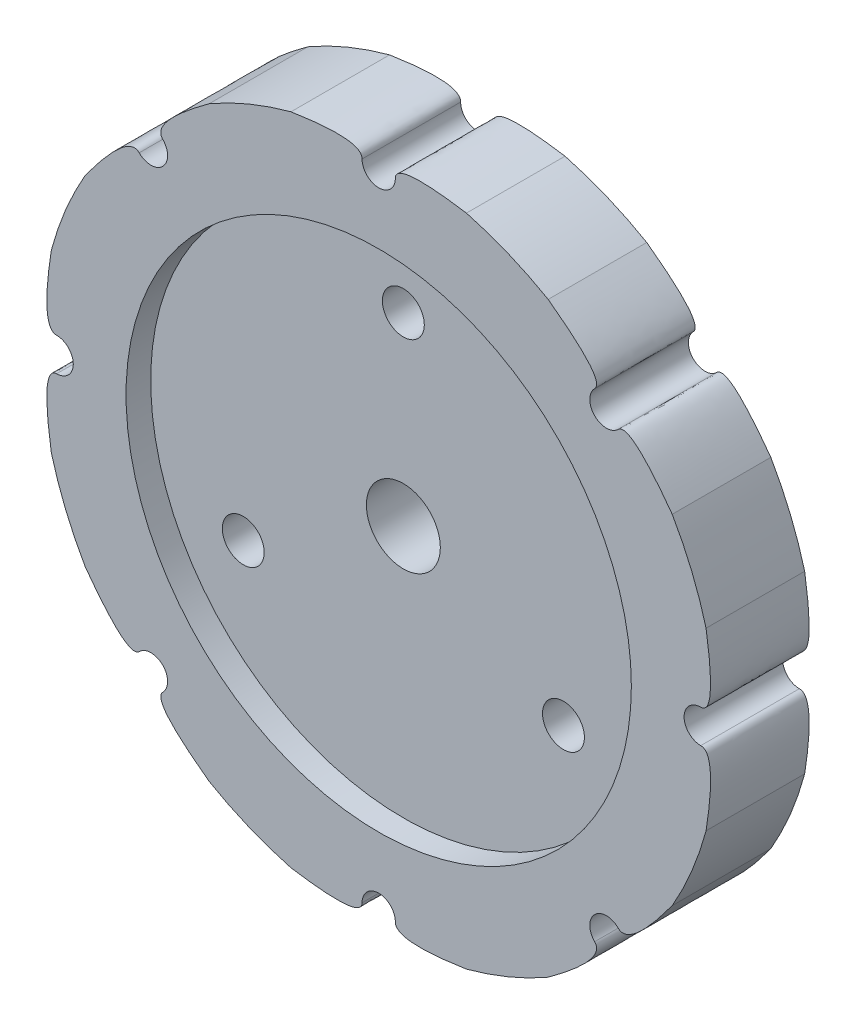
SolidWorks part; units mm, degrees
ref_plane "Plan de face" through (0, 0, 0) normal (0, 0, 1) x (1, 0, 0)
ref_plane "Plan de dessus" through (0, 0, 0) normal (0, 1, 0) x (1, 0, 0)
ref_plane "Plan de droite" through (0, 0, 0) normal (1, 0, 0) x (0, 0, -1)
sketch "Esquisse1" plane through (0, 0, 0) normal (0, 0, 1) x (1, 0, 0)
  circle A0 centre (0, 0) radius 27.5
  dimension "D1" = 55
extrude "Boss.-Extru.1" add sketch "Esquisse1" along normal mid plane 8
ref_axis "Axe1" through (0, 0, 4) along (0, 0, -1)
sketch "Esquisse2" plane through (0, 0, 0) normal (0, 0, 1) x (1, 0, 0)
  line L0 (0, 0) -> (0, 42.1559) construction
  line L1 (1.35, 26.1313) -> (1.35, 27.4668) construction
  line L2 (1.35, 27.4668) -> (7.1175, 26.563) construction
  line L3 (0, 0) -> (-7.1175, 26.563) construction
  line L4 (-1.35, 26.1313) -> (-1.35, 27.4668) construction
  line L5 (-1.35, 27.4668) -> (-7.1175, 26.563) construction
  line L6 (0, 0) -> (7.1175, 26.563) construction
  line L7 (0, 26.1313) -> (-18.4776, 18.4776) construction
  line L8 (-18.4776, 18.4776) -> (-26.1313, 0) construction
  line L9 (-26.1313, 0) -> (-18.4776, -18.4776) construction
  line L10 (-18.4776, -18.4776) -> (0, -26.1313) construction
  line L11 (0, -26.1313) -> (18.4776, -18.4776) construction
  line L12 (18.4776, -18.4776) -> (26.1313, 0) construction
  line L13 (26.1313, 0) -> (18.4776, 18.4776) construction
  line L14 (18.4776, 18.4776) -> (0, 26.1313) construction
  arc A0 (7.1175, 26.563) -> (-7.1175, 26.563) centre (0, 0) ccw
  circle A1 centre (0, 0) radius 26.1313 construction
  arc A2 (-1.35, 26.1313) -> (1.35, 26.1313) centre (0, 26.1313) ccw
  arc A4 (0, 26.1313) -> (18.4776, 18.4776) centre (0, 0) cw construction
  spline S0 degree 2 poles (1.35, 26.1313) (1.35, 27.4668) (7.1175, 26.563) knots 0 0 0 1 1 1
  spline S1 degree 2 poles (-1.35, 26.1313) (-1.35, 27.4668) (-7.1175, 26.563) knots 0 0 0 1 1 1
  dimension "D1" = 55
  dimension "D2" = 20
  dimension "D3" = 2.7
  dimension "D4" = 30
extrude "Enlèv. mat.-Extru.1" cut sketch "Esquisse2" against normal through all both and the other way through all
pattern_circular "Répétition circulaire1" count 8 over 360 about axis through (0, 0, 4) along (0, 0, -1) of "Enlèv. mat.-Extru.1"
hole_wizard "Diamètre du perçage Ø6.0 (6)1" positions "Esquisse5" profile "Esquisse4" hole size "Ø6.0" standard "Ansi Metric" end condition through all
sketch "Esquisse5" plane through (0, 0, 4) normal (0, 0, 1) x (1, 0, 0)
  point P0 (0, 0)
sketch "Esquisse4" plane through (0, 0, 4) normal (1, 0, 0) x (0, -1, 0)
  line L0 (0, 0) -> (0, 8)
  line L1 (0, 8) -> (3, 8)
  line L2 (3, 8) -> (3, 0)
  line L5 (3, 0) -> (0, 0)
  line L11 (0, -6.35) -> (0, 107.95) construction
  dimension "Diamètre du perçage jusqu'au prochain" = 6
  dimension "Profondeur du perçage jusqu'au prochain" = 8
sketch "Esquisse6" plane through (0, 0, 4) normal (0, 0, 1) x (1, 0, 0)
  line L0 (0, 26.0973) -> (0, 0.066) construction
  circle A0 centre (0, 26.0313) radius 1.25 construction
  arc A1 (-1.35, 26.1313) -> (1.35, 26.1313) centre (0, 26.1313) ccw construction
  dimension "D1" = 2.5
  dimension "rayon_pigonon" = 26.0313
hole_wizard "Dégagement M31" positions "Esquisse8" profile "Esquisse7" hole size "M3" standard "Ansi Metric" end condition through all
sketch "Esquisse8" plane through (0, 0, 4) normal (0, 0, 1) x (1, 0, 0)
  line L0 (0, 15) -> (-12.9904, -7.5)
  line L1 (-12.9904, -7.5) -> (12.9904, -7.5)
  line L2 (12.9904, -7.5) -> (0, 15)
  circle A0 centre (0, 0) radius 15
  point P0 (0, 15)
  point P2 (-12.9904, -7.5)
  point P4 (12.9904, -7.5)
  dimension "D1" = 30
sketch "Esquisse7" plane through (0, 15, 4) normal (1, 0, 0) x (0, -1, 0)
  line L0 (0, 0) -> (0, 8)
  line L1 (0, 8) -> (1.7, 8)
  line L2 (1.7, 8) -> (1.7, 0)
  line L5 (1.7, 0) -> (0, 0)
  line L11 (0, -6.35) -> (0, 107.95) construction
  dimension "Diamètre du perçage jusqu'au prochain" = 3.4
  dimension "Profondeur du perçage jusqu'au prochain" = 8
sketch "Esquisse9" plane through (0, 0, 4) normal (0, 0, 1) x (1, 0, 0)
  circle A0 centre (0, 0) radius 20.5
  dimension "D1" = 41
extrude "Enlèv. mat.-Extru.2" cut sketch "Esquisse9" against normal blind 2
equation "\"rayon_pignon\" = 26.0313"
